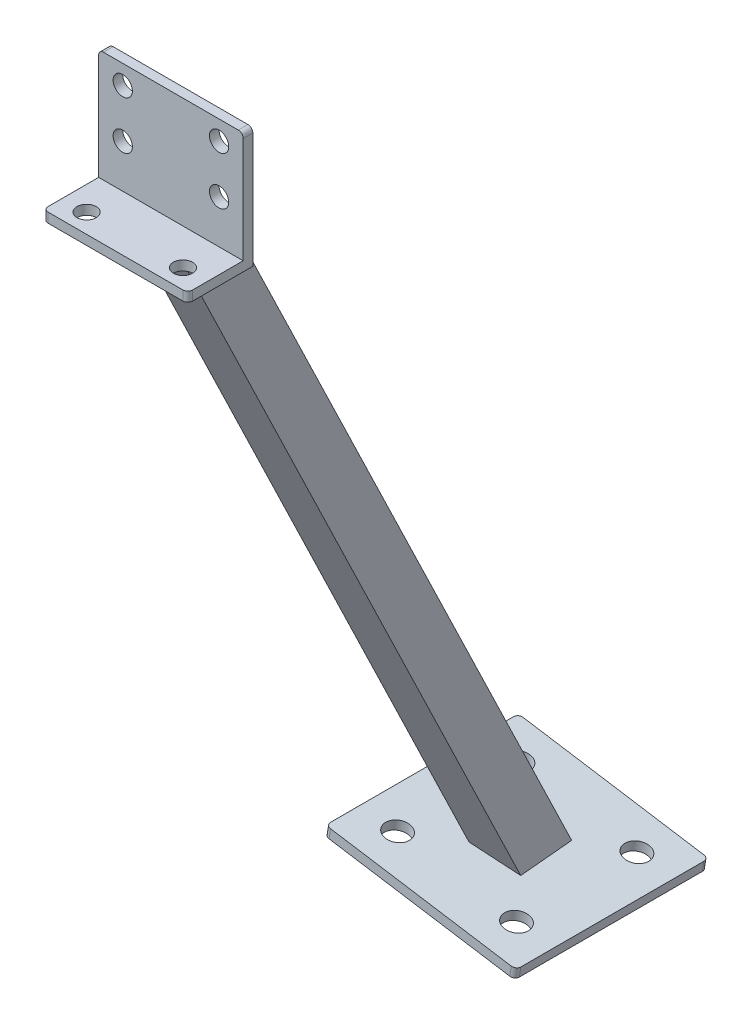
SolidWorks part; units mm, degrees
ref_plane "Front Plane" through (0, 0, 0) normal (0, 0, 1) x (1, 0, 0)
ref_plane "Top Plane" through (0, 0, 0) normal (0, 1, 0) x (1, 0, 0)
ref_plane "Right Plane" through (0, 0, 0) normal (1, 0, 0) x (0, 0, -1)
sketch "Sketch1" plane through (0, 0, 0) normal (1, 0, 0) x (0, 0, -1)
  line L0 (0, 0) -> (0, 50)
  line L1 (0, 50) -> (-4, 50)
  line L2 (-4, 50) -> (-4, 4)
  line L3 (-4, 4) -> (-27, 4)
  line L4 (-27, 4) -> (-27, 0)
  line L5 (-27, 0) -> (0, 0)
  dimension "D1" = 4
  dimension "D2" = 4
  dimension "D3" = 27
  dimension "D4" = 50
extrude "Boss-Extrude1" add sketch "Sketch1" along normal blind 60
ref_plane "Plane1" through (0, 0, 0) normal (0, -0.866, -0.5) x (-1, 0, 0)
sketch "Sketch2" plane through (0, 0, 0) normal (0, -0.866, -0.5) x (-1, 0, 0)
  line L0 (-30, 0) -> (-30, -23.3827)
  line L1 (-60, 0) -> (0, 0) construction
  line L2 (-60, -23.3827) -> (0, -23.3827) construction
ref_plane "Plane2" through (0.7342, 4.0142, 2.3176) normal (-0.1564, -0.8554, -0.4938) x (0, -0.5, 0.866)
sketch "Sketch3" plane through (0.7342, 4.0142, 2.3176) normal (-0.1564, -0.8554, -0.4938) x (0, -0.5, 0.866)
  line L0 (-9, -38.6307) -> (-9, -20.6307)
  line L1 (10, -39.6307) -> (-10, -39.6307)
  line L2 (10, -39.6307) -> (10, -19.6307)
  line L3 (10, -19.6307) -> (-10, -19.6307)
  line L4 (-10, -39.6307) -> (-10, -19.6307)
  line L5 (10, -39.6307) -> (-10, -19.6307) construction
  line L6 (10, -19.6307) -> (-10, -39.6307) construction
  line L7 (9, -20.6307) -> (-9, -20.6307)
  line L8 (9, -38.6307) -> (9, -20.6307)
  line L9 (9, -38.6307) -> (-9, -38.6307)
  point P0 (0, -29.6307)
  dimension "D1" = 20
  dimension "D2" = 20
  dimension "D3" = 1
extrude "Boss-Extrude2" add sketch "Sketch3" along normal blind 500 and the other way blind 20
sketch "Sketch5" plane through (0, 0, 0) normal (-1, 0, 0) x (0, 0, 1)
  line L0 (4, 4) -> (4, 36.0549)
  line L1 (4, 50) -> (4, 4) construction
  line L2 (4, 36.0549) -> (38.7814, 4)
  line L3 (4, 4) -> (27, 4) construction
  line L4 (38.7814, 4) -> (4, 4)
extrude "Cut-Extrude1" cut sketch "Sketch5" against normal blind 60
ref_plane "Plane3" through (-56.757, -358.3495, 0) normal (0.1564, 0.9877, 0) x (0.9877, -0.1564, 0)
sketch "Sketch7" plane through (-56.757, -358.3495, 0) normal (0.1564, 0.9877, 0) x (0.9877, -0.1564, 0)
  line L0 (19.2115, 0) -> (8.5312, 254.8002) construction
  line L1 (8.5312, 254.8002) -> (28.4656, 256.3645) construction
  line L3 (60.6025, 165.5937) -> (-19.3975, 165.5937)
  line L4 (60.6025, 165.5937) -> (60.6025, 245.5937)
  line L5 (60.6025, 245.5937) -> (-19.3975, 245.5937)
  line L6 (-19.3975, 165.5937) -> (-19.3975, 245.5937)
  line L7 (60.6025, 165.5937) -> (-19.3975, 245.5937) construction
  line L8 (60.6025, 245.5937) -> (-19.3975, 165.5937) construction
  point P0 (20.6025, 205.5937)
  point P5 (20.6025, 205.5937)
  dimension "D1" = 10
  dimension "D2" = 50
  dimension "D3" = 80
  dimension "D4" = 80
extrude "Boss-Extrude3" add sketch "Sketch7" along normal blind 4
sketch "Sketch8" plane through (-56.757, -358.3495, 0) normal (-0.1564, -0.9877, 0) x (0.9877, -0.1564, 0)
  line L1 (-25.4737, -284.3403) -> (70.9138, -284.3403)
  line L2 (-25.4737, -284.3403) -> (-25.4737, -180.2822)
  line L3 (-25.4737, -180.2822) -> (70.9138, -180.2822)
  line L4 (70.9138, -284.3403) -> (70.9138, -180.2822)
  line L5 (-25.4737, -284.3403) -> (70.9138, -180.2822) construction
  line L6 (-25.4737, -180.2822) -> (70.9138, -284.3403) construction
  point P0 (22.72, -232.3112)
extrude "Cut-Extrude3" cut sketch "Sketch8" along normal blind 100
sketch "Sketch9" plane through (0, 0, 0) normal (0, 0, -1) x (-1, 0, 0)
  circle A0 centre (-50, 22) radius 4 construction
  circle A1 centre (-10, 22) radius 4 construction
  circle A2 centre (-10, 42) radius 4 construction
  circle A3 centre (-50, 42) radius 4 construction
  circle A4 centre (-50, 22) radius 4
  circle A5 centre (-10, 22) radius 4
  circle A6 centre (-10, 42) radius 4
  circle A7 centre (-50, 42) radius 4
extrude "Cut-Extrude4" cut sketch "Sketch9" against normal up to next
sketch "Sketch10" plane through (0, 0, 0) normal (0, -1, 0) x (1, 0, 0)
  circle A0 centre (50, 19) radius 4 construction
  circle A1 centre (10, 19) radius 4 construction
  circle A2 centre (50, 19) radius 4
  circle A3 centre (10, 19) radius 4
extrude "Cut-Extrude5" cut sketch "Sketch10" against normal up to next
sketch "Sketch11" plane through (-56.757, -358.3495, 0) normal (-0.1564, -0.9877, 0) x (0.9877, -0.1564, 0)
  line L0 (-19.3975, -165.5937) -> (60.6025, -165.5937) construction
  line L1 (-19.3975, -245.5937) -> (-19.3975, -165.5937) construction
  circle A0 centre (-4.3975, -180.5937) radius 5
  circle A1 centre (45.6025, -180.5937) radius 5
  circle A2 centre (45.6025, -230.5937) radius 5
  circle A3 centre (-4.3975, -230.5937) radius 5
  dimension "D1" = 10
  dimension "D4" = 2
  dimension "D2" = 15
  dimension "D3" = 15
  dimension "D5" = 2
extrude "Cut-Extrude6" cut sketch "Sketch11" against normal up to next
fillet "Fillet1" radius 2 4 edges at (60, 2, 27) (0, 2, 27) (0, 50, 2) (60, 50, 2)
fillet "Fillet2" radius 2 4 edges at (3.4123, -365.8544, -245.5937) (-75.6028, -353.3397, -245.5937) (3.4123, -365.8544, -165.5937) (-75.6028, -353.3397, -165.5937)
